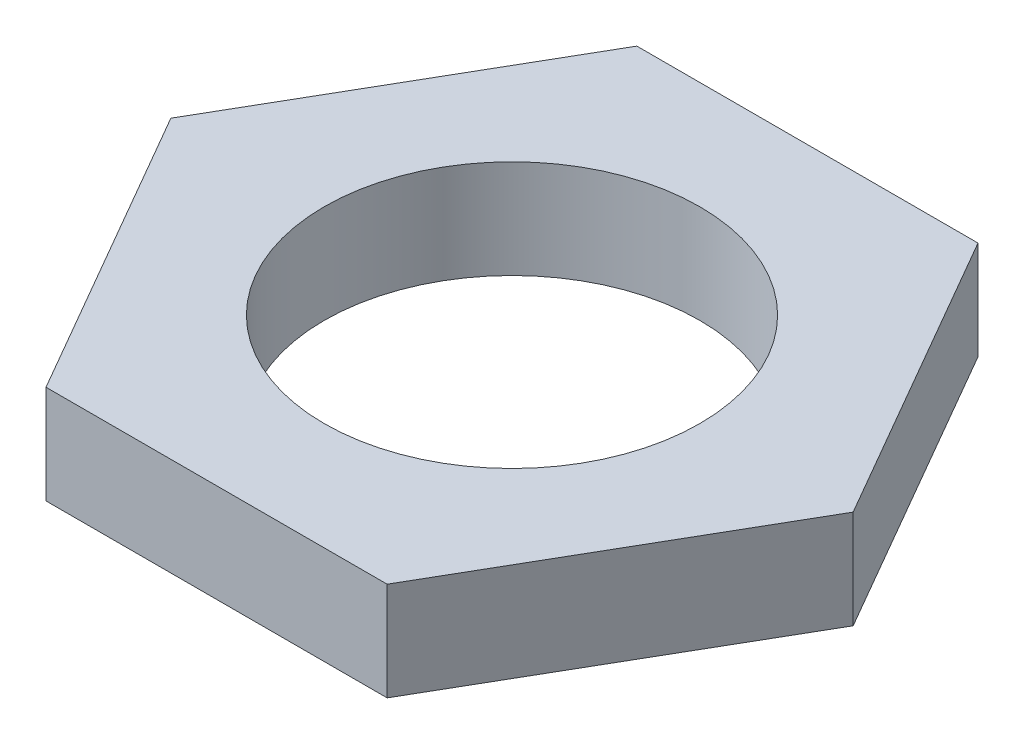
SolidWorks part; units mm, degrees
ref_plane "Front" through (0, 0, 0) normal (0, 0, 1) x (1, 0, 0)
ref_plane "Top" through (0, 0, 0) normal (0, 1, 0) x (1, 0, 0)
ref_plane "Right" through (0, 0, 0) normal (1, 0, 0) x (0, 0, -1)
sketch "Sketch1" plane through (0, 0, 0) normal (0, 1, 0) x (1, 0, 0)
  line L1 (4.5033, 0) -> (2.2517, 3.9)
  line L2 (2.2517, 3.9) -> (-2.2517, 3.9)
  line L3 (-2.2517, 3.9) -> (-4.5033, 0)
  line L4 (-4.5033, 0) -> (-2.2517, -3.9)
  line L5 (-2.2517, -3.9) -> (2.2517, -3.9)
  line L6 (2.2517, -3.9) -> (4.5033, 0)
  circle A0 centre (0, 0) radius 3.9 construction
  circle A1 centre (0, 0) radius 2.4795
  dimension "D2" = 4.959
  dimension "D1" = 7.8
extrude "Boss-Extrude1" add sketch "Sketch1" along normal blind 1.3
ref_plane "Plane1" through (0, -1, 0) normal (0, 1, 0) x (1, 0, 0)
sketch "Sketch4" plane through (0, -1, 0) normal (0, 1, 0) x (1, 0, 0)
  circle A0 centre (0, 0) radius 2.75
  dimension "D1" = 5.5
curve "Helix/Spiral2" pitch 0.5 height 2.875 radius 2.75 left hand yes centre (0, -1, 0) axis (0, 1, 0) start towards (0, 0, 1)
